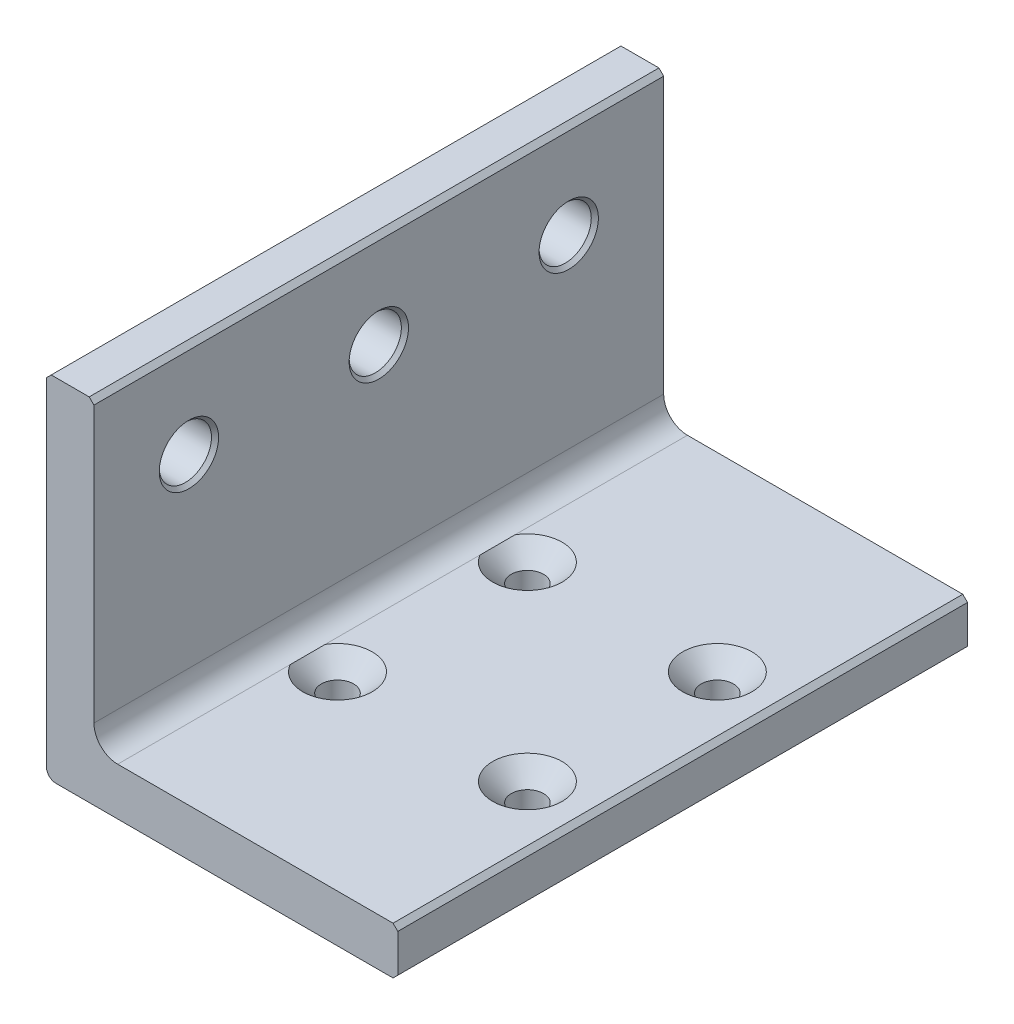
SolidWorks part; units mm, degrees
material "AISI 304"
ref_plane "Front Plane" through (0, 0, 0) normal (0, 0, 1) x (1, 0, 0)
ref_plane "Top Plane" through (0, 0, 0) normal (0, 1, 0) x (1, 0, 0)
ref_plane "Right Plane" through (0, 0, 0) normal (1, 0, 0) x (0, 0, -1)
sketch "Sketch1" plane through (0, 0, 0) normal (0, 0, 1) x (1, 0, 0)
  line L0 (-21.9455, 16.7077) -> (-21.9455, -18.7923)
  line L1 (-20.9455, -19.7923) -> (14.5545, -19.7923)
  line L2 (15.0545, -19.2923) -> (15.0545, -15.2923)
  line L3 (14.5545, -14.7923) -> (-14.4455, -14.7923)
  line L4 (-16.9455, -12.2923) -> (-16.9455, 16.7077)
  line L5 (-17.4455, 17.2077) -> (-21.4455, 17.2077)
  line L6 (-21.4455, 17.2077) -> (-21.9455, 16.7077)
  line L7 (-16.9455, 16.7077) -> (-17.4455, 17.2077)
  line L8 (15.0545, -15.2923) -> (14.5545, -14.7923)
  line L9 (14.5545, -19.7923) -> (15.0545, -19.2923)
  arc A0 (-14.4455, -14.7923) -> (-16.9455, -12.2923) centre (-14.4455, -12.2923) cw
  arc A1 (-21.9455, -18.7923) -> (-20.9455, -19.7923) centre (-20.9455, -18.7923) ccw
  point P0 (-21.9455, 17.2077)
  point P3 (15.0545, -19.7923)
  point P4 (15.0545, -14.7923)
  point P6 (-16.9455, 17.2077)
  point P18 (-21.9455, -19.7923)
  dimension "D5" = 2.5
  dimension "D6" = 1
  dimension "D1" = 37
  dimension "D2" = 37
  dimension "D3" = 5
  dimension "D4" = 5
extrude "Boss-Extrude1" add sketch "Sketch1" along normal blind 60
sketch "Sketch2" plane through (0, -14.7923, 0) normal (0, 1, 0) x (1, 0, 0)
  line L0 (15.0545, -60) -> (15.0545, 0) construction
  line L1 (14.5545, -60) -> (-14.4455, -60) construction
  circle A0 centre (8.7045, -40) radius 1
  circle A1 centre (8.7045, -20) radius 1
  circle A2 centre (-11.2955, -20) radius 1
  circle A3 centre (-11.2955, -40) radius 1
  dimension "D1" = 20
  dimension "D2" = 20
  dimension "D3" = 20
  dimension "D4" = 20
  dimension "D5" = 6.35
  dimension "D6" = 20
hole_wizard "CSK for M3 Flat Head Machine Screw1" positions "3DSketch1" profile "Sketch3" countersink size "M3" standard "ANSI Metric" end condition through all
sketch3d "3DSketch1"
  point P0 (-11.2955, -14.7923, 40)
  point P3 (8.7045, -14.7923, 40)
  point P6 (8.7045, -14.7923, 20)
  point P9 (-11.2955, -14.7923, 20)
sketch "Sketch3" plane through (-11.2955, -14.7923, 40) normal (1, 0, 0) x (0, 0, 1)
  line L0 (0, 0) -> (0, 5)
  line L1 (0, 5) -> (2, 5)
  line L2 (1.7, 4.7) -> (1.7, 1.95)
  line L3 (1.7, 1.95) -> (3.65, 0)
  line L5 (3.65, 0) -> (0, 0)
  line L6 (-1.7, 1.95) -> (-3.65, 0) construction
  line L7 (2, 5) -> (1.7, 4.7)
  line L8 (-2, 5) -> (-1.7, 4.7) construction
  line L11 (0, -6.35) -> (0, 107.95) construction
  dimension "Thru Hole Dia." = 3.4
  dimension "Thru Hole Depth" = 5
  dimension "Near C'Sink Dia." = 7.3
  dimension "Near C'Sink Angle" = 90
  dimension "Far C'Sink Dia." = 4
  dimension "Far C'Sink Angle" = 90
sketch "Sketch4" plane through (-16.9455, 0, 0) normal (1, 0, 0) x (0, 0, -1)
  line L0 (-60, -12.2923) -> (-60, 16.7077) construction
  line L1 (-60, 17.2077) -> (0, 17.2077) construction
  circle A0 centre (-50, 7.2077) radius 1
  circle A1 centre (-30, 7.2077) radius 1
  circle A2 centre (-10, 7.2077) radius 1
  dimension "D1" = 20
  dimension "D2" = 20
  dimension "D3" = 10
  dimension "D4" = 10
hole_wizard "M5 Clearance Hole1" positions "3DSketch2" profile "Sketch5" hole size "M5" standard "ANSI Metric" end condition through all
sketch3d "3DSketch2"
  point P0 (-16.9455, 7.2077, 50)
  point P3 (-16.9455, 7.2077, 30)
  point P6 (-16.9455, 7.2077, 10)
sketch "Sketch5" plane through (-16.9455, 7.2077, 50) normal (0, 1, 0) x (0, 0, -1)
  line L0 (0, 0) -> (0, 5)
  line L1 (0, 5) -> (3.125, 5)
  line L2 (2.75, 4.625) -> (2.75, 0.375)
  line L3 (2.75, 0.375) -> (3.125, 0)
  line L5 (3.125, 0) -> (0, 0)
  line L6 (-2.75, 0.375) -> (-3.125, 0) construction
  line L7 (3.125, 5) -> (2.75, 4.625)
  line L8 (-3.125, 5) -> (-2.75, 4.625) construction
  line L11 (0, -6.35) -> (0, 107.95) construction
  dimension "Thru Hole Dia." = 5.5
  dimension "Thru Hole Depth" = 5
  dimension "Near C'Sink Dia." = 6.25
  dimension "Near C'Sink Angle" = 90
  dimension "Far C'Sink Dia." = 6.25
  dimension "Far C'Sink Angle" = 90
